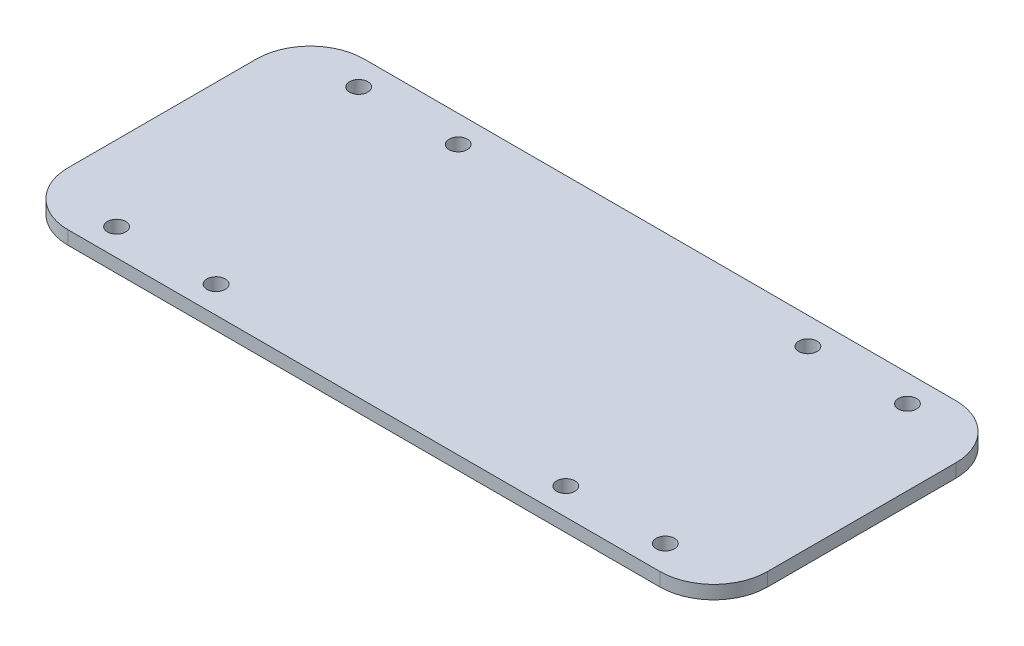
SolidWorks part; units mm, degrees
ref_plane "Front Plane" through (0, 0, 0) normal (0, 0, 1) x (1, 0, 0)
ref_plane "Top Plane" through (0, 0, 0) normal (0, 1, 0) x (1, 0, 0)
ref_plane "Right Plane" through (0, 0, 0) normal (1, 0, 0) x (0, 0, -1)
sketch "Sketch1" plane through (0, 0, 0) normal (0, 1, 0) x (1, 0, 0)
  line L1 (10, 0) -> (120, 0)
  line L2 (0, 10) -> (0, 45)
  line L3 (10, 55) -> (120, 55)
  line L4 (130, 10) -> (130, 45)
  arc A0 (10, 55) -> (0, 45) centre (10, 45) ccw
  arc A1 (0, 10) -> (10, 0) centre (10, 10) ccw
  arc A2 (130, 10) -> (120, 0) centre (120, 10) cw
  arc A3 (120, 55) -> (130, 45) centre (120, 45) cw
  point P7 (0, 55)
  point P10 (0, 0)
  point P13 (130, 0)
  dimension "D3" = 10
  dimension "D4" = 10
  dimension "D5" = 10
  dimension "D6" = 10
  dimension "D1" = 130
  dimension "D2" = 55
extrude "Boss-Extrude1" add sketch "Sketch1" along normal blind 2.5
sketch "Sketch2" plane through (0, 2.5, 0) normal (0, 1, 0) x (1, 0, 0)
  line L0 (0, 45) -> (0, 10) construction
  line L1 (10, 0) -> (120, 0) construction
  line L2 (120, 55) -> (10, 55) construction
  line L3 (65, 55) -> (65, 0) construction
  circle A0 centre (14, 5) radius 1.7
  circle A1 centre (14, 50) radius 1.7
  circle A2 centre (116, 5) radius 1.7
  circle A3 centre (116, 50) radius 1.7
  point P16 (0, 0)
  dimension "D2" = 14
  dimension "D3" = 5
  dimension "D5" = 5
extrude "Cut-Extrude1" cut sketch "Sketch2" against normal through all
sketch "Sketch3" plane through (0, 2.5, 0) normal (0, 1, 0) x (1, 0, 0)
  circle A1 centre (32.5, 50) radius 1.7
  circle A2 centre (32.5, 5) radius 1.7
  circle A3 centre (97.5, 5) radius 1.7
  circle A4 centre (97.5, 50) radius 1.7
  point P13 (0, 0)
  point P14 (0, 0)
extrude "Cut-Extrude2" cut sketch "Sketch3" against normal blind 10
